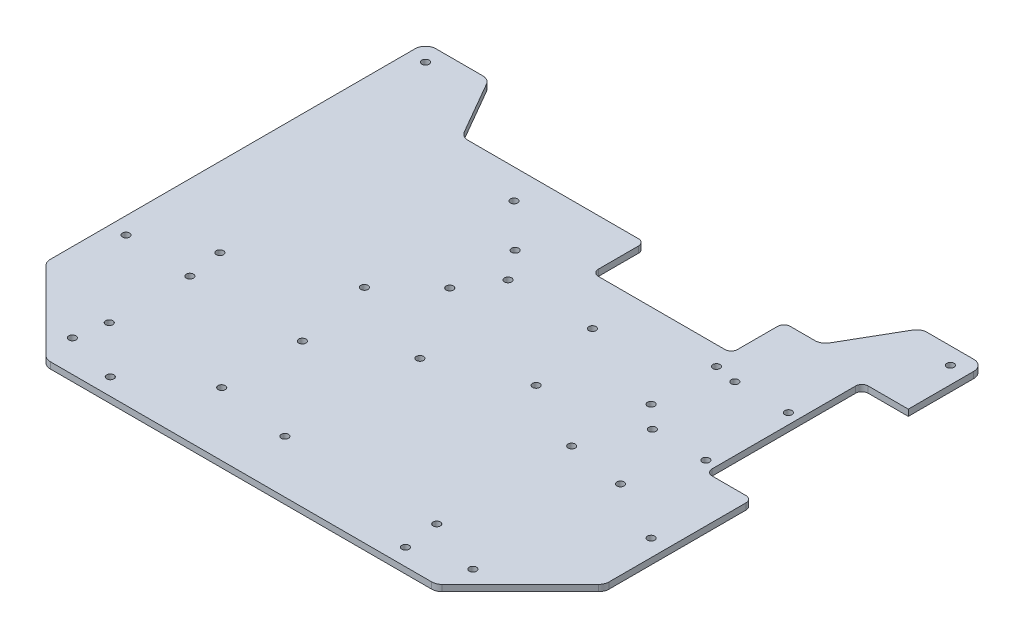
SolidWorks part; units mm, degrees
material "Acier non allié"
ref_plane "Front" through (0, 0, 0) normal (0, 0, 1) x (1, 0, 0)
ref_plane "Top" through (0, 0, 0) normal (0, 1, 0) x (1, 0, 0)
ref_plane "Right" through (0, 0, 0) normal (1, 0, 0) x (0, 0, -1)
sketch "Esquisse1" plane through (0, 0, 0) normal (0, 1, 0) x (1, 0, 0)
  line L0 (0, 0) -> (0, 190) construction
  line L1 (-92.5, 0) -> (92.5, 0)
  line L2 (92.5, 0) -> (132.5, 40)
  line L3 (132.5, 40) -> (132.5, 220)
  line L4 (132.5, 220) -> (102.5, 220)
  line L5 (102.5, 220) -> (85.1795, 190)
  line L6 (85.1795, 190) -> (-85.1795, 190)
  line L7 (-102.5, 220) -> (-85.1795, 190)
  line L8 (-132.5, 220) -> (-102.5, 220)
  line L9 (-132.5, 40) -> (-132.5, 220)
  line L10 (-92.5, 0) -> (-132.5, 40)
  dimension "D1" = 132.5
  dimension "D2" = 220
  dimension "D3" = 60
  dimension "D4" = 30
  dimension "D5" = 40
  dimension "D6" = 40
  dimension "D7" = 30
extrude "Boss.-Extru.1" add sketch "Esquisse1" along normal blind 3
fillet "Congé1" radius 5 10 edges at (92.5, 1.5, 0) (132.5, 1.5, -40) (132.5, 1.5, -220) (102.5, 1.5, -220) (85.1795, 1.5, -190) (-85.1795, 1.5, -190) (-102.5, 1.5, -220) (-132.5, 1.5, -220) (-92.5, 1.5, 0) (-132.5, 1.5, -40)
sketch "Esquisse2" plane through (0, 3, 0) normal (0, 1, 0) x (1, 0, 0)
  line L0 (0, 0) -> (0, 294.1173) construction
  line L2 (-90.4289, 0) -> (90.4289, 0) construction
  circle A0 centre (70, 8) radius 1
  circle A1 centre (124.5, 70) radius 1
  circle A2 centre (124.5, 212) radius 1
  circle A3 centre (-124.5, 212) radius 1
  circle A4 centre (-124.5, 70) radius 1
  circle A5 centre (-70, 8) radius 1
  dimension "D2" = 2
  dimension "D6" = 2
  dimension "D9" = 2
  dimension "D1" = 70
  dimension "D3" = 8
  dimension "D4" = 124.5
  dimension "D5" = 70
  dimension "D7" = 124.5
  dimension "D8" = 212
extrude "Enlèv. mat.-Extru.1" cut sketch "Esquisse2" against normal blind 3
hole_wizard "Dégagement M31" positions "Esquisse3" profile "Esquisse4" hole size "M3" standard "ISO" end condition through all
sketch "Esquisse3" plane through (0, 3, 0) normal (0, 1, 0) x (1, 0, 0)
  point P0 (70, 8)
  point P3 (-70, 8)
  point P6 (-124.5, 70)
  point P9 (-124.5, 212)
  point P12 (124.5, 212)
  point P15 (124.5, 70)
sketch "Esquisse4" plane through (70, 3, -8) normal (1, 0, 0) x (0, 0, 1)
  line L0 (0, 0) -> (0, 3)
  line L1 (0, 3) -> (1.7, 3)
  line L2 (1.7, 3) -> (1.7, 0)
  line L5 (1.7, 0) -> (0, 0)
  line L11 (0, -6.35) -> (0, 107.95) construction
  dimension "Diamètre du perçage jusqu'au prochain" = 3.4
  dimension "Profondeur du perçage jusqu'au prochain" = 3
sketch "Esquisse5" plane through (0, 3, 0) normal (0, 1, 0) x (1, 0, 0)
  line L0 (82.2927, 190) -> (-82.2927, 190) construction
  line L1 (67.5, 190) -> (1.5, 190)
  line L2 (67.5, 190) -> (67.5, 165)
  line L3 (67.5, 165) -> (1.5, 165)
  line L4 (1.5, 190) -> (1.5, 165)
  line L5 (132.5, 42.0711) -> (132.5, 215) construction
  line L6 (132.5, 184) -> (110.5, 184)
  line L7 (132.5, 184) -> (132.5, 110)
  line L8 (132.5, 110) -> (110.5, 110)
  line L9 (110.5, 184) -> (110.5, 110)
  line L10 (127.5, 220) -> (105.3868, 220) construction
  dimension "D1" = 25
  dimension "D2" = 65
  dimension "D3" = 131
  dimension "D4" = 36
  dimension "D5" = 110
  dimension "D6" = 22
extrude "Enlèv. mat.-Extru.2" cut sketch "Esquisse5" against normal through all
fillet "Congé2" radius 3 7 edges at (132.5, 1.5, -110) (110.5, 1.5, -110) (110.5, 1.5, -184) (67.5, 1.5, -190) (67.5, 1.5, -165) (1.5, 1.5, -165) (1.5, 1.5, -190)
sketch "Esquisse6" plane through (0, 3, 0) normal (0, 1, 0) x (1, 0, 0)
  line L0 (110.5, 140.5) -> (-167.6757, 140.5) construction
  line L1 (110.5, 181) -> (110.5, 113) construction
  line L2 (-90.4289, 0) -> (90.4289, 0) construction
  line L3 (110.5, 181) -> (110.5, 113) construction
  circle A0 centre (69.5, 156) radius 1
  circle A1 centre (-26, 156) radius 1
  circle A2 centre (-46.5, 176) radius 1
  circle A3 centre (69.5, 125) radius 1
  circle A4 centre (-26, 125) radius 1
  circle A5 centre (-46.5, 105) radius 1
  dimension "D4" = 2
  dimension "D6" = 2
  dimension "D10" = 2
  dimension "D1" = 140.5
  dimension "D2" = 41
  dimension "D3" = 15.5
  dimension "D5" = 136.5
  dimension "D7" = 15.5
  dimension "D8" = 35.5
  dimension "D9" = 157
extrude "Enlèv. mat.-Extru.3" cut sketch "Esquisse6" against normal through all
hole_wizard "Dégagement M32" positions "Esquisse7" profile "Esquisse8" hole size "M3" standard "ISO"
sketch "Esquisse7" plane through (0, 3, 0) normal (0, 1, 0) x (1, 0, 0)
  point P0 (-46.5, 105)
  point P3 (-26, 125)
  point P6 (-26, 156)
  point P9 (-46.5, 176)
  point P12 (69.5, 156)
  point P15 (69.5, 125)
sketch "Esquisse8" plane through (-46.5, 3, -105) normal (1, 0, 0) x (0, 0, 1)
  line L0 (0, 0) -> (0, 11.0215)
  line L1 (0, 11.0215) -> (1.7, 10)
  line L2 (1.7, 10) -> (1.7, 0)
  line L5 (1.7, 0) -> (0, 0)
  line L10 (0, 11.0215) -> (-1.7, 10) construction
  line L11 (0, -6.35) -> (0, 107.95) construction
  dimension "Diamètre du perçage" = 3.4
  dimension "Profondeur du perçage" = 10
  dimension "Angle de pointe" = 118
sketch "Esquisse9" plane through (0, 3, 0) normal (0, 1, 0) x (1, 0, 0)
  line L0 (132.5, 42.0711) -> (132.5, 107) construction
  line L1 (-90.4289, 0) -> (90.4289, 0) construction
  line L2 (-132.5, 215) -> (-132.5, 42.0711) construction
  line L3 (-39.16, 30) -> (-92.5, 30) construction
  line L4 (-39.16, 30) -> (-39.16, 68.24) construction
  line L5 (-39.16, 68.24) -> (-92.5, 68.24) construction
  line L6 (-92.5, 30) -> (-92.5, 68.24) construction
  line L7 (-4.16, 25) -> (-4.16, 89) construction
  line L8 (4.5, 165) -> (64.5, 165) construction
  line L9 (24.5, 142.1606) -> (-15.5, 142.1606) construction
  line L10 (110.5, 181) -> (110.5, 113) construction
  line L11 (113.5, 110) -> (129.5, 110) construction
  circle A0 centre (105.5, 115) radius 1
  circle A3 centre (105.5, 154.12) radius 1
  circle A6 centre (-92.5, 68.24) radius 1
  circle A7 centre (-39.16, 68.24) radius 1
  circle A8 centre (-39.16, 30) radius 1
  circle A9 centre (-92.5, 30) radius 1
  circle A10 centre (-4.16, 89) radius 1
  circle A11 centre (67.84, 89) radius 1
  circle A12 centre (-4.16, 25) radius 1
  circle A13 centre (67.84, 25) radius 1
  circle A14 centre (-15.5, 142.1606) radius 1
  circle A15 centre (24.5, 142.1606) radius 1
  circle A16 centre (34.5, 105.5) radius 1
  circle A17 centre (80.1, 115) radius 1
  circle A18 centre (80.1, 154.12) radius 1
  point P40 (0, 0)
  point P43 (67.6662, 92.5)
  dimension "D2" = 2
  dimension "D4" = 2
  dimension "D17" = 2
  dimension "D18" = 2
  dimension "D19" = 2
  dimension "D20" = 2
  dimension "D21" = 2
  dimension "D22" = 2
  dimension "D23" = 2
  dimension "D24" = 2
  dimension "D32" = 2
  dimension "D33" = 2
  dimension "D34" = 2
  dimension "D11" = 2
  dimension "D12" = 2
  dimension "D5" = 27
  dimension "25" = 27
  dimension "D10" = 39.12
  dimension "D13" = 38.24
  dimension "D14" = 53.34
  dimension "D15" = 30
  dimension "D16" = 40
  dimension "D25" = 72
  dimension "D26" = 72
  dimension "D27" = 64
  dimension "D28" = 64
  dimension "D29" = 35
  dimension "D30" = 25
  dimension "D31" = 25
  dimension "D36" = 38
  dimension "D37" = 40
  dimension "D39" = 10
  dimension "D7" = 5
  dimension "D8" = 25.4
  dimension "D9" = 25.4
  dimension "D40" = 39.12
  dimension "D35" = 59.5
  dimension "D38" = 76
extrude "Enlèv. mat.-Extru.4" cut sketch "Esquisse9" against normal through all
hole_wizard "Dégagement M33" positions "Esquisse10" profile "Esquisse11" hole size "M3" standard "ISO"
sketch "Esquisse10" plane through (0, 3, 0) normal (0, 1, 0) x (1, 0, 0)
  point P3 (105.5, 115)
  point P9 (105.5, 154.12)
  point P14 (80.1, 154.12)
  point P17 (80.1, 115)
sketch "Esquisse11" plane through (105.5, 3, -115) normal (1, 0, 0) x (0, 0, 1)
  line L0 (0, 0) -> (0, 11.0215)
  line L1 (0, 11.0215) -> (1.7, 10)
  line L2 (1.7, 10) -> (1.7, 0)
  line L5 (1.7, 0) -> (0, 0)
  line L10 (0, 11.0215) -> (-1.7, 10) construction
  line L11 (0, -6.35) -> (0, 107.95) construction
  dimension "Diamètre du perçage" = 3.4
  dimension "Profondeur du perçage" = 10
  dimension "Angle de pointe" = 118
sketch "Esquisse12" plane through (0, 3, 0) normal (0, 1, 0) x (1, 0, 0)
  line L2 (-90.4289, 0) -> (90.4289, 0) construction
  line L3 (95, 15) -> (-95, 15) construction
  line L4 (95, 15) -> (95, 85) construction
  line L5 (95, 85) -> (-95, 85) construction
  line L6 (-95, 15) -> (-95, 85) construction
  line L7 (132.5, 42.0711) -> (132.5, 107) construction
  circle A4 centre (-95, 85) radius 1
  circle A5 centre (95, 85) radius 1
  circle A6 centre (95, 15) radius 1
  circle A7 centre (-95, 15) radius 1
  point P6 (95, 50)
  dimension "D5" = 2
  dimension "D6" = 2
  dimension "D7" = 2
  dimension "D8" = 2
  dimension "D1" = 70
  dimension "D2" = 190
  dimension "D3" = 15
  dimension "D4" = 37.5
extrude "Enlèv. mat.-Extru.5" cut sketch "Esquisse12" against normal through all and the other way through all
hole_wizard "Dégagement M34" positions "Esquisse13" profile "Esquisse14" hole size "M3" standard "ISO"
sketch "Esquisse13" plane through (0, 3, 0) normal (0, 1, 0) x (1, 0, 0)
  point P3 (-92.5, 68.24)
  point P6 (-92.5, 30)
  point P9 (-39.16, 30)
  point P12 (-39.16, 68.24)
  point P16 (-4.16, 25)
  point P19 (67.84, 25)
  point P22 (-4.16, 89)
  point P25 (67.84, 89)
  point P29 (34.5, 105.5)
  point P32 (24.5, 142.1606)
  point P35 (-15.5, 142.1606)
sketch "Esquisse14" plane through (-92.5, 3, -68.24) normal (1, 0, 0) x (0, 0, 1)
  line L0 (0, 0) -> (0, 11.0215)
  line L1 (0, 11.0215) -> (1.7, 10)
  line L2 (1.7, 10) -> (1.7, 0)
  line L5 (1.7, 0) -> (0, 0)
  line L10 (0, 11.0215) -> (-1.7, 10) construction
  line L11 (0, -6.35) -> (0, 107.95) construction
  dimension "Diamètre du perçage" = 3.4
  dimension "Profondeur du perçage" = 10
  dimension "Angle de pointe" = 118
hole_wizard "Dégagement M35" positions "Esquisse15" profile "Esquisse16" hole size "M3" standard "ISO"
sketch "Esquisse15" plane through (0, 3, 0) normal (0, 1, 0) x (1, 0, 0)
  point P0 (-95, 15)
  point P3 (-95, 85)
  point P6 (95, 85)
  point P9 (95, 15)
sketch "Esquisse16" plane through (-95, 3, -15) normal (1, 0, 0) x (0, 0, 1)
  line L0 (0, 0) -> (0, 11.0215)
  line L1 (0, 11.0215) -> (1.7, 10)
  line L2 (1.7, 10) -> (1.7, 0)
  line L5 (1.7, 0) -> (0, 0)
  line L10 (0, 11.0215) -> (-1.7, 10) construction
  line L11 (0, -6.35) -> (0, 107.95) construction
  dimension "Diamètre du perçage" = 3.4
  dimension "Profondeur du perçage" = 10
  dimension "Angle de pointe" = 118
equation "\"WIDTH\"= 300mm'Total width of the robot"
equation "\"LENGTH\"= 220mm'Total length of the robot"
equation "\"CUT_DEPTH\"= 45mm'Depth of the cut on the edges of the plate"
equation "\"Plate_th\"= 3mm'Thickness of the plate"
equation "\"D1\"= \"Plate_th\""
equation "\"D5@Esquisse9\"=\"25@Esquisse9\""
